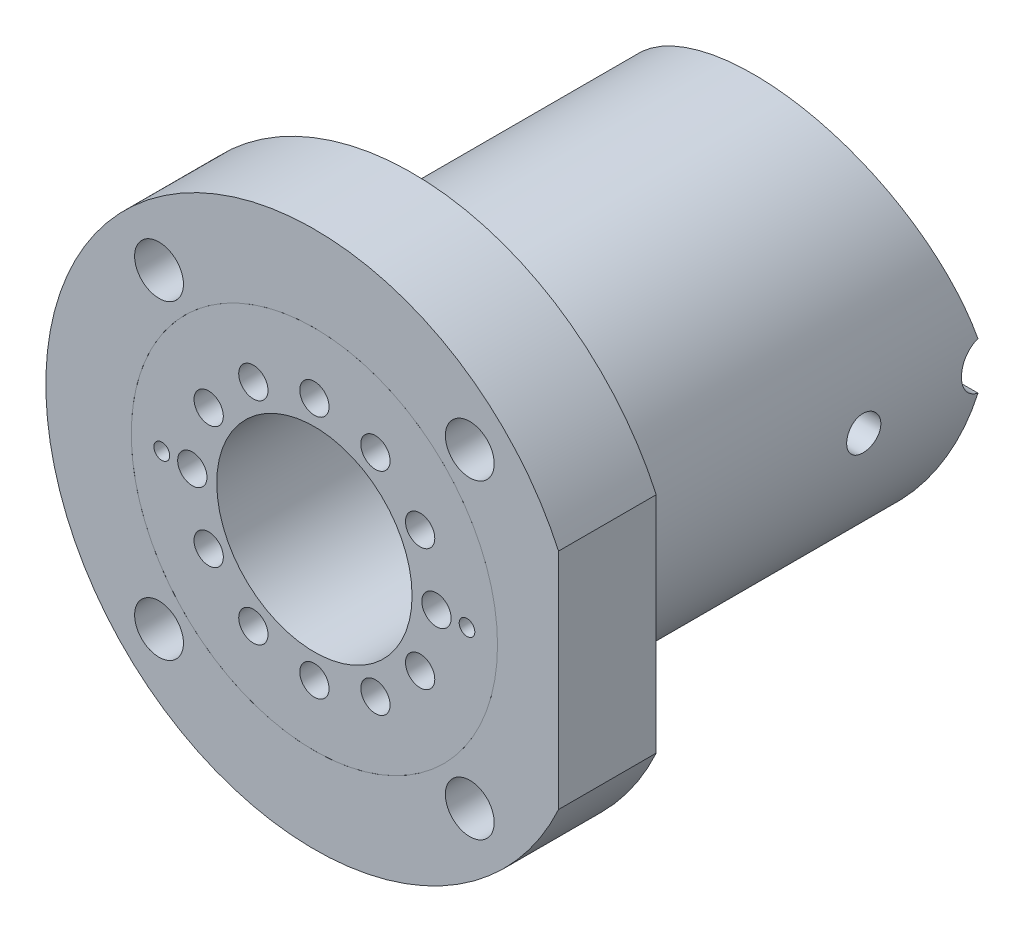
SolidWorks part; units mm, degrees
material "3.0205 (EN-AW 1200)"
ref_plane "前视基准面" through (0, 0, 0) normal (0, 0, 1) x (1, 0, 0)
ref_plane "上视基准面" through (0, 0, 0) normal (0, 1, 0) x (1, 0, 0)
ref_plane "右视基准面" through (0, 0, 0) normal (1, 0, 0) x (0, 0, -1)
sketch "草图1" plane through (0, 0, 0) normal (0, 0, 1) x (1, 0, 0)
  line L0 (0, 0) -> (-6.25, 0) construction
  line L1 (-6.25, 0) -> (6.25, 0) construction
  circle A0 centre (0, 0) radius 7.5
  circle A1 centre (0, 0) radius 4
  circle A2 centre (0, 0) radius 5 construction
  circle A29 centre (0, 5) radius 0.6
  circle A30 centre (2.5, 4.3301) radius 0.6
  circle A31 centre (4.3301, 2.5) radius 0.6
  circle A32 centre (5, 0) radius 0.6
  circle A33 centre (4.3301, -2.5) radius 0.6
  circle A34 centre (2.5, -4.3301) radius 0.6
  circle A35 centre (0, -5) radius 0.6
  circle A36 centre (-2.5, -4.3301) radius 0.6
  circle A37 centre (-4.3301, -2.5) radius 0.6
  circle A38 centre (-5, 0) radius 0.6
  circle A39 centre (-4.3301, 2.5) radius 0.6
  circle A40 centre (-2.5, 4.3301) radius 0.6
  circle A41 centre (0, 0) radius 6.25 construction
  circle A42 centre (-6.25, 0) radius 0.325
  circle A43 centre (6.25, 0) radius 0.32
  point P19 (0, 0)
  point P20 (0, 0)
  point P32 (0, 0)
  point P35 (0, 0)
  dimension "D1" = 10
  dimension "D2" = 15
  dimension "D3" = 8
  dimension "D4" = 1.2
  dimension "D6" = 12.5
  dimension "D7" = 0.64
  dimension "D8" = 0.65
  dimension "D5" = 12
extrude "凸台-拉伸1" add sketch "草图1" along normal blind 20
sketch "草图2" plane through (0, 0, 0) normal (1, 0, 0) x (0, 0, -1)
  line L0 (0, 0) -> (-2.0096, 7.5)
  line L1 (-2.0096, 7.5) -> (0, 7.5)
  line L2 (0, 7.5) -> (0, 0)
  line L3 (0, 7.5) -> (-20, 7.5) construction
  dimension "D1" = 15
extrude "切除-拉伸1" cut sketch "草图2" against normal through all and the other way through all
mirror "镜向1" about plane through (0, 0, 0) normal (0, 1, 0) of "切除-拉伸1"
sketch "草图3" plane through (0, 0, 20) normal (0, 0, 1) x (1, 0, 0)
  line L0 (0, 0) -> (10, 0) construction
  line L1 (10, 4.5826) -> (10, -4.5826)
  arc A0 (10, 4.5826) -> (10, -4.5826) centre (0, 0) ccw
  circle A1 centre (0, 0) radius 7.5
extrude "凸台-拉伸2" add sketch "草图3" against normal blind 4 separate body
sketch "草图5" plane through (0, 0, 20) normal (0, 0, 1) x (1, 0, 0)
  line L1 (-6.364, -6.364) -> (6.364, -6.364) construction
  line L2 (-6.364, -6.364) -> (-6.364, 6.364) construction
  line L3 (-6.364, 6.364) -> (6.364, 6.364) construction
  line L4 (6.364, -6.364) -> (6.364, 6.364) construction
  line L5 (-6.364, -6.364) -> (6.364, 6.364) construction
  line L6 (-6.364, 6.364) -> (6.364, -6.364) construction
  circle A0 centre (0, 0) radius 9 construction
  circle A1 centre (-6.364, 6.364) radius 1
  circle A2 centre (6.364, 6.364) radius 1
  circle A3 centre (-6.364, -6.364) radius 1
  circle A4 centre (6.364, -6.364) radius 1
extrude "切除-拉伸2" cut sketch "草图5" against normal blind 4
sketch "草图6" plane through (0, 0, 0) normal (1, 0, 0) x (0, 0, -1)
  circle A0 centre (0, 0) radius 1
  dimension "D1" = 2
extrude "切除-拉伸3" cut sketch "草图6" against normal blind 10 and the other way blind 10
ref_plane "基准面1" through (-7.5, 0, 0) normal (-1, 0, 0) x (0, 0, 1)
sketch "草图8" plane through (-7.5, 0, 0) normal (-1, 0, 0) x (0, 0, 1)
  line L0 (0, 0) -> (20, 0) construction
  line L1 (20, -11) -> (20, 11) construction
  circle A0 centre (5, 0) radius 0.7
  dimension "D1" = 1.4
  dimension "D2" = 5
extrude "切除-拉伸4" cut sketch "草图8" against normal blind 1.25
pattern_circular "阵列(圆周)1" count 2 over 360 about axis through (0, 0, 20) along (0, 0, -1) of "切除-拉伸4" reverse direction yes
